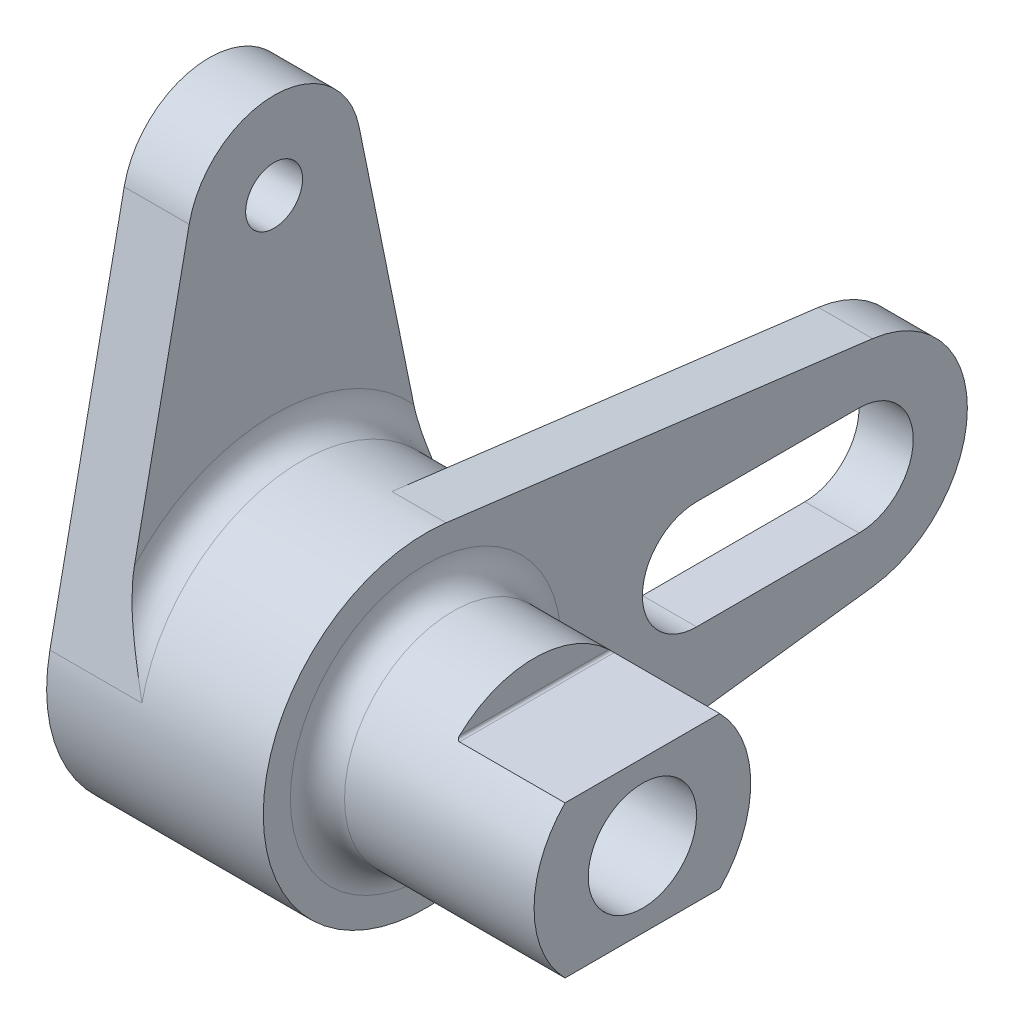
SolidWorks part; units mm, degrees
ref_plane "Piano frontale" through (0, 0, 0) normal (0, 0, 1) x (1, 0, 0)
ref_plane "Piano superiore" through (0, 0, 0) normal (0, 1, 0) x (1, 0, 0)
ref_plane "Piano destro" through (0, 0, 0) normal (1, 0, 0) x (0, 0, -1)
sketch "Schizzo1" plane through (0, 0, 0) normal (0, 0, 1) x (1, 0, 0)
  line L0 (0, 0) -> (94.4755, 0) construction
  line L1 (0, 10) -> (80, 10)
  line L2 (80, 10) -> (80, 20)
  line L5 (80, 20) -> (40, 20)
  line L6 (40, 20) -> (40, 30)
  line L7 (40, 30) -> (0, 30)
  line L8 (0, 30) -> (0, 10)
  line L9 (0, 10) -> (0, 0) construction
  point P7 (94.4755, 0)
  dimension "D1" = 20
  dimension "D2" = 60
  dimension "D3" = 40
  dimension "D4" = 80
  dimension "D5" = 40
revolve "Rivoluzione1" add sketch "Schizzo1" angle 360 about L0
sketch "Schizzo3" plane through (0, 0, 0) normal (1, 0, 0) x (0, 0, -1)
  line L0 (0, 70) -> (0, 0) construction
  line L1 (-15.6767, 73.2) -> (-29.3939, 6)
  line L2 (15.6767, 73.2) -> (29.3939, 6)
  arc A0 (15.6767, 73.2) -> (-15.6767, 73.2) centre (0, 70) ccw
  circle A3 centre (0, 0) radius 30 construction
  arc A4 (-29.3939, 6) -> (29.3939, 6) centre (0, 0) ccw
  circle A7 centre (0, 0) radius 10 construction
  circle A8 centre (0, 0) radius 10
  point P4 (0, 0)
  point P9 (33.3233, -13.2501)
  point P11 (-35.4647, -23.7406)
  dimension "D1" = 16
  dimension "D2" = 70
extrude "Estrusione-Estrusione1" add sketch "Schizzo3" along normal blind 12
sketch "Schizzo4" plane through (40, 0, 0) normal (1, 0, 0) x (0, 0, -1)
  line L0 (0, 0) -> (80, 0) construction
  line L1 (3.75, 29.7647) -> (82.5, 19.8431)
  line L2 (3.75, -29.7647) -> (82.5, -19.8431)
  line L3 (80, 0) -> (50, 0) construction
  line L4 (80, -10) -> (50, -10)
  line L5 (80, 10) -> (50, 10)
  arc A0 (82.5, -19.8431) -> (82.5, 19.8431) centre (80, 0) ccw
  arc A1 (80, -10) -> (80, 10) centre (80, 0) ccw
  circle A2 centre (0, 0) radius 30
  arc A3 (3.75, 29.7647) -> (3.75, -29.7647) centre (0, 0) ccw
  arc A4 (50, 10) -> (50, -10) centre (50, 0) ccw
  circle A5 centre (0, 0) radius 10 construction
  circle A6 centre (0, 0) radius 10
  point P4 (65, 0)
  dimension "D2" = 40
  dimension "D5" = 10
  dimension "D3" = 80
  dimension "D4" = 30
  dimension "D1" = 0
extrude "Estrusione-Estrusione2" add sketch "Schizzo4" against normal blind 10
sketch "Schizzo5" plane through (80, 0, 0) normal (1, 0, 0) x (0, 0, -1)
  line L1 (-20, -14) -> (20, -14)
  line L2 (-20, -14) -> (-20, 14)
  line L3 (-20, 14) -> (20, 14)
  line L4 (20, -14) -> (20, 14)
  line L5 (-20, -14) -> (20, 14) construction
  line L6 (-20, 14) -> (20, -14) construction
  circle A1 centre (0, 0) radius 20 construction
  point P0 (0, 0)
  dimension "D1" = 28
extrude "Taglio-Estrusione1" cut sketch "Schizzo5" against normal blind 20 flip side to cut
fillet "Raccordo1" radius 0.5 2 edges at (60, 14, 0) (60, -14, 0)
fillet "Raccordo2" radius 5 2 edges at (12, 30, 0) (40, 0, 20)
hole_wizard "Foro filettato M12x1.5-1" positions "Schizzo8" profile "Schizzo9" tap size "M12x1.5" standard "ISO" end condition through all
sketch "Schizzo8" plane through (12, 0, 0) normal (1, 0, 0) x (0, 0, -1)
  point P0 (0, 70)
sketch "Schizzo9" plane through (12, 70, 0) normal (0, 1, 0) x (0, 0, -1)
  line L0 (0, 0) -> (0, 12)
  line L1 (0, 12) -> (5.25, 12)
  line L2 (5.25, 12) -> (5.25, 0)
  line L5 (5.25, 0) -> (0, 0)
  line L11 (0, -6.35) -> (0, 107.95) construction
  dimension "Thru Tap Drill Dia." = 10.5
  dimension "Thru Tap Drill Depth" = 12
cosmetic thread "Filettatura del foro1" parameters "D2"=12
